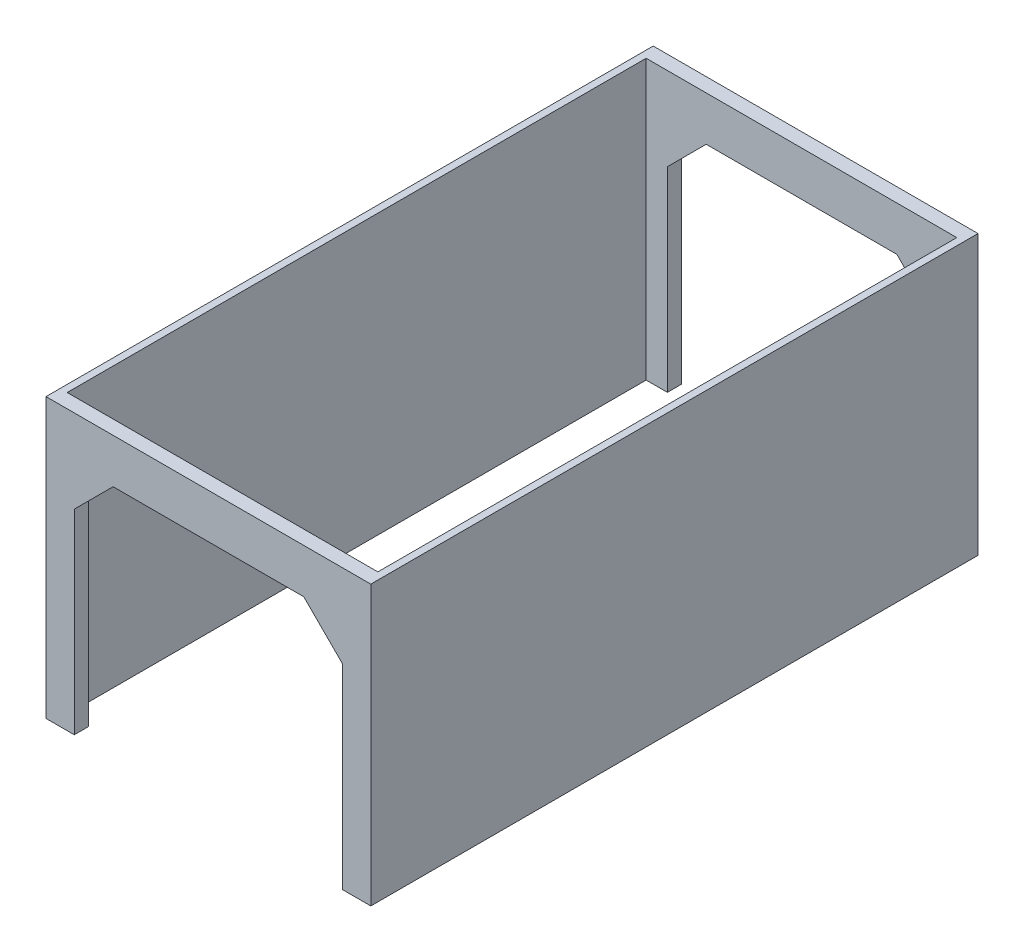
SolidWorks part; units mm, degrees
ref_plane "Front Plane" through (0, 0, 0) normal (0, 0, 1) x (1, 0, 0)
ref_plane "Top Plane" through (0, 0, 0) normal (0, 1, 0) x (1, 0, 0)
ref_plane "Right Plane" through (0, 0, 0) normal (1, 0, 0) x (0, 0, -1)
sketch "Sketch1" plane through (0, 0, 0) normal (0, 0, 1) x (1, 0, 0)
  line L0 (0, 122) -> (230, 122)
  line L1 (0, 122) -> (0, 0)
  line L2 (0, 0) -> (50, 0)
  line L5 (50, 30) -> (28.532, 30)
  line L8 (20.032, 63) -> (47.532, 90.5)
  line L9 (47.532, 90.5) -> (182.5591, 90.5)
  line L10 (115, 122) -> (115, -49.5124) construction
  line L11 (210.0591, 63) -> (182.5591, 90.5)
  line L12 (210.0591, 38.5) -> (210.0591, 63)
  line L14 (201.468, 30) -> (201.5591, 30)
  line L17 (230, 0) -> (180, 0)
  line L18 (230, 122) -> (230, 0)
  line L21 (50, 30) -> (50, 0)
  line L22 (180, 30) -> (180, 0)
  line L23 (20.032, 63) -> (20.032, 38.5)
  line L24 (20.032, 38.5) -> (28.532, 38.5)
  line L25 (28.532, 38.5) -> (28.532, 30)
  line L26 (201.5591, 38.5) -> (201.5591, 30)
  line L27 (210.0591, 38.5) -> (201.5591, 38.5)
  line L28 (210.0591, 63) -> (210.0591, 38.5)
  line L29 (180, 30) -> (180, 0)
  line L30 (210.0591, 63) -> (182.5591, 90.5)
  line L31 (201.468, 30) -> (201.5591, 30)
  line L32 (230, 0) -> (180, 0)
  line L33 (230, 122) -> (230, 0)
  line L34 (201.468, 38.5) -> (201.468, 30)
  line L35 (209.968, 38.5) -> (201.468, 38.5)
  line L36 (209.968, 63) -> (209.968, 38.5)
  line L37 (180, 30) -> (180, 0)
  line L38 (182.468, 90.5) -> (47.4409, 90.5)
  line L39 (209.968, 63) -> (182.468, 90.5)
  line L40 (180, 30) -> (201.468, 30)
  line L41 (230, 0) -> (180, 0)
  line L42 (230, 122) -> (230, 0)
  point P15 (115.0455, 90.5)
  dimension "D2" = 122
  dimension "D3" = 31.5
  dimension "D4" = 50
  dimension "D5" = 30
  dimension "D6" = 135
  dimension "D7" = 24.5
  dimension "D8" = 38.8909
  dimension "D9" = 8.5
  dimension "D10" = 135.0271
  dimension "D11" = 20.032
  dimension "D12" = 21.468
  dimension "D13" = 28.532
  dimension "D14" = 38.5
  dimension "D15" = 8.5
  dimension "D16" = 63
  dimension "D17" = 230
  dimension "D18" = 115.0455
  dimension "D19" = 90.5
  dimension "D20" = 2.468
  dimension "D22" = 47.532
extrude "Boss-Extrude5" add sketch "Sketch1" along normal blind 430 contours L0 L10 L38 L9 L11 L12 L27 L26 L14 L40 L22 L17 L18 | L10 L0 L1 L2 L21 L5 L25 L24 L23 L8 L9 region at (57.5, 120.3234, 0) region at (172.5, 120.3234, 0)
sketch "Sketch6" plane through (0, 122, 0) normal (0, 1, 0) x (1, 0, 0)
  line L1 (0, 0) -> (230, 0)
  line L2 (0, 0) -> (0, -430)
  line L3 (0, -430) -> (230, -430)
  line L4 (230, 0) -> (230, -430)
  line L5 (5, -10) -> (225, -10)
  line L6 (5, -10) -> (5, -420)
  line L7 (5, -420) -> (225, -420)
  line L8 (225, -10) -> (225, -420)
  dimension "D1" = 10
  dimension "D2" = 10
  dimension "D3" = 5
  dimension "D4" = 5
extrude "Cut-Extrude5" cut sketch "Sketch6" against normal blind 430 contours L6 L5 L8 L7
sketch "Sketch7" plane through (0, 0, 10) normal (0, 0, 1) x (1, 0, 0)
  line L0 (5, 0) -> (50, 0) construction
  line L1 (50, 30) -> (43, 30)
  line L2 (50, 30) -> (50, 0)
  line L3 (50, 0) -> (43, 0)
  line L4 (43, 30) -> (43, 0)
  line L5 (225, 0) -> (180, 0) construction
  line L6 (180, 30) -> (187, 30)
  line L7 (180, 30) -> (180, 0)
  line L8 (180, 0) -> (187, 0)
  line L9 (187, 30) -> (187, 0)
  dimension "D1" = 7
  dimension "D2" = 7
extrude "Boss-Extrude6" add sketch "Sketch7" along normal blind 30 contours L2 L1 L4 L3 | L7 L6 L9 L8
sketch "Sketch8" plane through (0, 0, 420) normal (0, 0, -1) x (-1, 0, 0)
  line L0 (-225, 0) -> (-180, 0) construction
  line L1 (-180, 30) -> (-187, 30)
  line L2 (-180, 30) -> (-180, 0)
  line L3 (-180, 0) -> (-187, 0)
  line L4 (-187, 30) -> (-187, 0)
  line L5 (-5, 0) -> (-50, 0) construction
  line L6 (-50, 30) -> (-43, 30)
  line L7 (-50, 30) -> (-50, 0)
  line L8 (-50, 0) -> (-43, 0)
  line L9 (-43, 30) -> (-43, 0)
  dimension "D1" = 7
  dimension "D2" = 7
extrude "Boss-Extrude7" add sketch "Sketch8" along normal blind 30
sketch "Sketch9" plane through (0, 0, 0) normal (0, -1, 0) x (1, 0, 0)
  line L0 (0, 0) -> (50, 0) construction
  line L1 (0, 430) -> (5, 430)
  line L2 (0, 430) -> (0, 0)
  line L3 (0, 0) -> (5, 0)
  line L4 (5, 420) -> (5, 10)
  line L6 (50, 430) -> (50, 390) construction
  line L7 (5, 430) -> (50, 430)
  line L9 (5, 420) -> (43, 420)
  line L10 (50, 430) -> (50, 420)
  line L11 (47.532, 420) -> (182.5591, 420) construction
  line L14 (43, 420) -> (43, 390)
  line L15 (43, 390) -> (50, 390)
  line L16 (50, 420) -> (50, 390)
  line L17 (5, 10) -> (43, 10)
  line L19 (5, 0) -> (50, 0)
  line L20 (50, 10) -> (50, 0)
  line L22 (43, 10) -> (43, 40)
  line L23 (43, 40) -> (50, 40)
  line L24 (50, 10) -> (50, 40)
  line L26 (225, 420) -> (225, 10)
  line L27 (225, 0) -> (230, 0)
  line L28 (230, 420) -> (230, 0)
  line L29 (187, 10) -> (225, 10)
  line L31 (187, 0) -> (230, 0)
  line L32 (230, 10) -> (230, 0)
  line L33 (180, 40) -> (187, 40)
  line L34 (180, 40) -> (180, 0)
  line L35 (180, 0) -> (187, 0)
  line L36 (187, 40) -> (187, 10)
  line L37 (225, 420) -> (187, 420)
  line L38 (230, 420) -> (230, 430)
  line L39 (230, 430) -> (180, 430)
  line L40 (180, 420) -> (180, 430)
  line L42 (187, 420) -> (187, 390)
  line L43 (187, 390) -> (180, 390)
  line L44 (180, 420) -> (180, 390)
  line M2 (5, 10) -> (5, 420)
  line M3 (5, 420) -> (43, 420)
  line M4 (43, 420) -> (43, 390)
  line M5 (43, 390) -> (50, 390)
  line M6 (50, 390) -> (50, 430)
  line M7 (50, 430) -> (0, 430)
  line M8 (0, 430) -> (0, 0)
  line M9 (0, 0) -> (50, 0)
  line M10 (50, 0) -> (50, 40)
  line M11 (50, 40) -> (43, 40)
  line M12 (43, 40) -> (43, 10)
  line M13 (43, 10) -> (5, 10)
  dimension "D1" = 5
extrude "Boss-Extrude8" add sketch "Sketch9" along normal blind 28 contours M13 M2 M3 M4 M5 M6 M7 M8 M9 M10 M11 M12 | L40 L44 L43 L42 L37 L26 L29 L36 L33 L34 L35 L31 L27 L28 L38 L39 region at (2.5, 0, 425.671) region at (206, 0, 424.329)
sketch "Sketch10" plane through (0, 0, 0) normal (0, 0, -1) x (-1, 0, 0)
  line L0 (-50, 30) -> (-28.532, 30)
  line L2 (-20.032, 38.5) -> (-20.032, -28)
  line L3 (-20.032, -28) -> (-50, -28)
  line L4 (-50, 30) -> (-50, -28)
  line L6 (-210.0591, 63) -> (-210.0591, -28)
  line L7 (-210.0591, -28) -> (-180, -28)
  line L8 (-180, 30) -> (-180, -28)
  line L10 (-20.032, 38.5) -> (-20.032, -28)
  line L11 (-20.032, -28) -> (-50, -28)
  line L12 (-50, 30) -> (-50, -28)
  line L14 (-50, 30) -> (-50, -28)
  line L15 (-50, -28) -> (-20.032, -28)
  line L16 (-20.032, 30) -> (-20.032, -28)
  line L17 (-28.532, 30) -> (-28.532, 38.5)
  line L18 (-28.532, 38.5) -> (-20.032, 38.5)
  line L19 (-210.0591, 38.5) -> (-201.5591, 38.5)
  line L20 (-201.5591, 38.5) -> (-201.5591, 30)
  line L21 (-201.5591, 30) -> (-180, 30)
  line L22 (-50, 30) -> (-28.532, 30)
  line M3 (-230, -28) -> (-180, -28)
  line M4 (-180, -28) -> (-180, 30)
  line M5 (-180, 30) -> (-201.5591, 30)
  line M6 (-201.5591, 30) -> (-201.5591, 38.5)
  line M7 (-201.5591, 38.5) -> (-210.0591, 38.5)
  line M13 (-20.032, 38.5) -> (-28.532, 38.5)
  line M14 (-28.532, 38.5) -> (-28.532, 30)
  line M15 (-28.532, 30) -> (-50, 30)
  line M16 (-50, 30) -> (-50, -28)
  line M17 (-50, -28) -> (0, -28)
extrude "Cut-Extrude6" cut sketch "Sketch10" against normal up to surface (430 mm away) contours L6 M7 M3 M4 M5 M6 | L2 L10 M13 M14 M15 M16 M17 region at (34.5876, 2.327, 0) region at (195.4585, 2.3231, 0) up to face at (115.0253, 39.6111, 430)
sketch "Sketch11" plane through (0, -28, 0) normal (0, -1, 0) x (1, 0, 0)
  line L1 (230, 0) -> (225, 0)
  line L2 (230, 0) -> (230, 420)
  line L4 (225, 10) -> (225, 420)
  line L5 (210.0591, 430) -> (230, 430)
  line L6 (210.0591, 430) -> (210.0591, 420)
  line L7 (210.0591, 420) -> (225, 420)
  line L8 (230, 430) -> (230, 420)
  line L9 (225, 0) -> (210.0591, 0)
  line L11 (225, 10) -> (210.0591, 10)
  line L12 (210.0591, 0) -> (210.0591, 10)
  line L14 (5, 10) -> (5, 420)
  line L15 (5, 430) -> (0, 430)
  line L16 (0, 10) -> (0, 430)
  line L17 (20.032, 420) -> (5, 420)
  line L18 (20.032, 420) -> (20.032, 430)
  line L19 (20.032, 430) -> (5, 430)
  line L21 (20.032, 0) -> (0, 0)
  line L22 (20.032, 0) -> (20.032, 10)
  line L23 (20.032, 10) -> (5, 10)
  line L24 (0, 0) -> (0, 10)
extrude "Boss-Extrude9" add sketch "Sketch11" along normal blind 38.4
sketch "Sketch12" plane through (0, 0, 0) normal (-1, 0, 0) x (0, 0, 1)
  line L0 (430, 122) -> (430, -66.4) construction
  line L1 (0, -66.4) -> (430, -66.4)
  line L2 (0, -66.4) -> (0, -60.4)
  line L3 (0, -60.4) -> (430, -60.4)
  line L4 (430, -66.4) -> (430, -60.4)
  dimension "D1" = 6
extrude "Cut-Extrude7" cut sketch "Sketch12" against normal blind 500
sketch "Sketch13" plane through (0, -60.4, 0) normal (0, -1, 0) x (1, 0, 0)
  line L1 (0, 430) -> (5, 430)
  line L2 (0, 430) -> (0, 10)
  line L3 (0, 10) -> (5, 10)
  line L4 (5, 430) -> (5, 10)
  line L5 (0, 0) -> (20.032, 0)
  line L6 (0, 0) -> (0, 10)
  line L7 (0, 10) -> (20.032, 10)
  line L8 (20.032, 0) -> (20.032, 10)
  line L9 (5, 420) -> (20.032, 420)
  line L10 (5, 420) -> (5, 430)
  line L11 (5, 430) -> (20.032, 430)
  line L12 (20.032, 420) -> (20.032, 430)
  line M1 (20.032, 0) -> (20.032, 10)
  line M2 (20.032, 10) -> (5, 10)
  line M3 (5, 10) -> (5, 420)
  line M4 (5, 420) -> (20.032, 420)
  line M5 (20.032, 420) -> (20.032, 430)
  line M6 (20.032, 430) -> (0, 430)
  line M7 (0, 430) -> (0, 0)
  line M8 (0, 0) -> (20.032, 0)
extrude "Boss-Extrude10" add sketch "Sketch13" along normal blind 15 contours L4 M6 M4 M5 | L4 L3 M6 M7 M3 | L3 M7 M8 M1 M2 region at (2.5, -60.4, 220) region at (12.516, -60.4, 425) region at (10.016, -60.4, 5)
sketch "Sketch14" plane through (0, -60.4, 0) normal (0, -1, 0) x (1, 0, 0)
  line L1 (230, 430) -> (225, 430)
  line L2 (230, 430) -> (230, 10)
  line L3 (230, 10) -> (225, 10)
  line L4 (225, 430) -> (225, 10)
  line L5 (230, 0) -> (210.0591, 0)
  line L6 (230, 0) -> (230, 10)
  line L7 (230, 10) -> (210.0591, 10)
  line L8 (210.0591, 0) -> (210.0591, 10)
  line L9 (230, 430) -> (210.0591, 430)
  line L10 (230, 430) -> (230, 420)
  line L11 (230, 420) -> (210.0591, 420)
  line L12 (210.0591, 430) -> (210.0591, 420)
  line M1 (230, 0) -> (230, 430)
  line M2 (230, 430) -> (210.0591, 430)
  line M3 (210.0591, 430) -> (210.0591, 420)
  line M4 (210.0591, 420) -> (225, 420)
  line M5 (225, 420) -> (225, 10)
  line M6 (225, 10) -> (210.0591, 10)
  line M7 (210.0591, 10) -> (210.0591, 0)
  line M8 (210.0591, 0) -> (230, 0)
extrude "Boss-Extrude11" add sketch "Sketch14" along normal blind 15 contours L4 M2 M3 M4 | L11 L2 L4 M2 | L11 L3 M1 M5 | L3 M1 M6 M7 M8 region at (227.5, -60.4, 425) region at (217.5295, -60.4, 425) region at (227.5, -60.4, 215) region at (220.0295, -60.4, 5)
